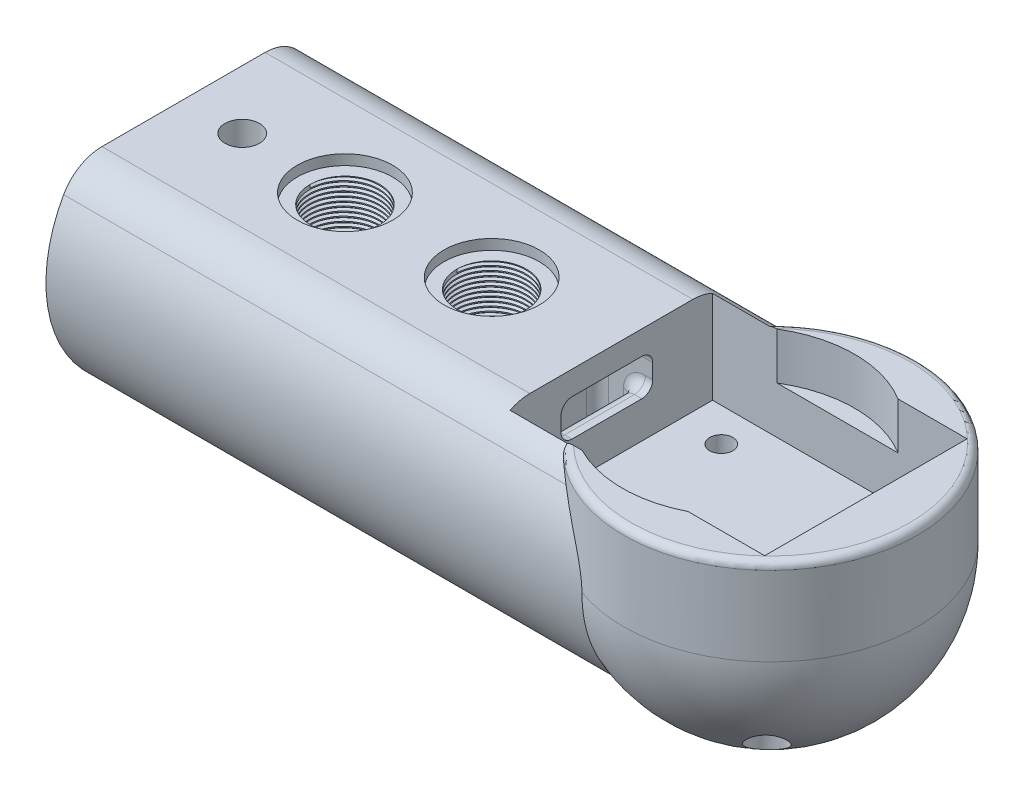
SolidWorks part; units mm, degrees
ref_plane "Front Plane" through (0, 0, 0) normal (0, 0, 1) x (1, 0, 0)
ref_plane "Top Plane" through (0, 0, 0) normal (0, 1, 0) x (1, 0, 0)
ref_plane "Right Plane" through (0, 0, 0) normal (1, 0, 0) x (0, 0, -1)
sketch "Sketch1" plane through (0, 0, 0) normal (1, 0, 0) x (0, 0, -1)
  circle A0 centre (0, 0) radius 18.75
  dimension "D1" = 37.5
extrude "Boss-Extrude1" add sketch "Sketch1" along normal blind 80
sketch "Sketch2" plane through (0, 0, 0) normal (1, 0, 0) x (0, 0, -1)
  circle A0 centre (0, 0) radius 3
  dimension "D1" = 6
extrude "Cut-Extrude1" cut sketch "Sketch2" along normal blind 12
sketch "Sketch3" plane through (0, 0, 0) normal (1, 0, 0) x (0, 0, -1)
  circle A0 centre (0, 0) radius 5.9
  dimension "D1" = 11.8
extrude "Cut-Extrude3" cut sketch "Sketch3" along normal blind 3
ref_plane "Plane1" through (0, 18.75, 0) normal (0, 1, 0) x (1, 0, 0)
sketch "Sketch5" plane through (0, 0, 0) normal (0, 1, 0) x (1, 0, 0)
  line L0 (0, 0) -> (65, 0) construction
  line L1 (80, -18.75) -> (80, 18.75) construction
  line L2 (80, 0) -> (100, 0) construction
  line L3 (100, 0) -> (109.7094, 0) construction
  line L4 (80, 0) -> (65, 0) construction
  line L5 (80, 0) -> (80, -42.3157) construction
  line L6 (80, 20) -> (80, -20)
  arc A0 (80, -20) -> (80, 20) centre (80, 0) ccw
  dimension "D1" = 40
revolve "Revolve95" add sketch "Sketch5" angle 180 about L5 reverse direction yes
sketch "Sketch23" plane through (0, 18.75, 0) normal (0, 1, 0) x (1, 0, 0)
  line L0 (80, -18.75) -> (73.0403, -18.75) construction
  line L1 (0, 18.75) -> (85, 18.75)
  line L2 (0, 18.75) -> (0, -18.75)
  line L3 (0, -18.75) -> (85, -18.75)
  line L4 (85, 18.75) -> (85, -18.75)
extrude "Cut-Extrude14" cut sketch "Sketch23" against normal blind 6.5
ref_plane "Plane7" through (0, 0, 0) normal (0, 1, 0) x (1, 0, 0)
sketch "Sketch26" plane through (0, 0, 0) normal (0, 1, 0) x (1, 0, 0)
  line L0 (0, 0) -> (118.1144, 0) construction
  line L1 (80, -18.75) -> (80, 18.75) construction
  circle A0 centre (80, 0) radius 20
  dimension "D1" = 40
extrude "Boss-Extrude8" add sketch "Sketch26" along normal blind 12.5
ref_plane "Plane9" through (0, 12.5, 0) normal (0, 1, 0) x (1, 0, 0)
fillet "Fillet9" radius 6 2 edges at (32.9555, 12.25, -14.1951) (32.9555, 12.25, 14.1951)
sketch "Sketch28" plane through (0, 12.5, 0) normal (0, 1, 0) x (1, 0, 0)
  line L0 (0, 0) -> (117.3111, 0) construction
  line L2 (58.3, 13.8) -> (93, 13.8)
  line L3 (58.3, 13.8) -> (58.3, -13.8)
  line L4 (58.3, -13.8) -> (93, -13.8)
  line L5 (93, 13.8) -> (93, -13.8)
  circle A0 centre (80, 0) radius 20 construction
  point P13 (100, 0)
  dimension "D1" = 34.7
  dimension "D2" = 27.6
  dimension "D3" = 13.8
  dimension "D4" = 7
extrude "Cut-Extrude16" cut sketch "Sketch28" against normal blind 13.5
ref_plane "Plane10" through (0, -1, 0) normal (0, 1, 0) x (1, 0, 0)
sketch "Sketch29" plane through (0, -1, 0) normal (0, 1, 0) x (1, 0, 0)
  line L0 (0, 0) -> (112.771, 0) construction
  line L1 (93, -13.8) -> (93, 13.8) construction
  line L2 (75.5, 24.0476) -> (75.5, -24.0476) construction
  line L3 (93, 13.8) -> (65.5238, 13.8) construction
  line L5 (93, -13.8) -> (93, 13.8) construction
  line L6 (89.92, -10.43) -> (64.07, -10.43) construction
  line L7 (64.07, 18.499) -> (64.07, -18.499) construction
  line L8 (89.92, 9.22) -> (64.07, 9.22) construction
  circle A0 centre (89.92, 9.22) radius 1.575
  circle A5 centre (89.92, -10.43) radius 1.575
  circle A7 centre (64.07, -10.43) radius 1.575
  circle A8 centre (64.07, 9.22) radius 1.575
  point P3 (75.5, 0)
  point P9 (75.5, 0)
  point P32 (64.07, 0)
  dimension "D2" = 3.15
  dimension "D5" = 19.65
  dimension "D1" = 17.5
  dimension "D3" = 4.58
  dimension "D4" = 3.08
  dimension "D6" = 25.85
extrude "Cut-Extrude17" cut sketch "Sketch29" against normal blind 13.5
ref_plane "Plane11" through (0, 12.5, 0) normal (0, 1, 0) x (1, 0, 0)
ref_plane "Plane13" through (58.3, 0, 0) normal (1, 0, 0) x (0, 0, -1)
sketch "Sketch31" plane through (58.3, 0, 0) normal (1, 0, 0) x (0, 0, -1)
  line L0 (15.18, -1) -> (-15.18, -1) construction
  line L1 (-6.85, 9) -> (5.65, 9)
  line L2 (-6.85, 9) -> (-6.85, 4)
  line L3 (-6.85, 4) -> (5.65, 4)
  line L4 (5.65, 9) -> (5.65, 4)
  line L5 (-13.8, -1) -> (-13.8, 12.5) construction
  point P8 (-13.8, 5.75)
  point P9 (-6.85, 6.5)
  dimension "D1" = 5
  dimension "D2" = 12.5
  dimension "D3" = 5
  dimension "D4" = 6.95
ref_plane "Plane17" through (0, 12.25, 0) normal (0, 1, 0) x (1, 0, 0)
sketch "Sketch35" plane through (0, 12.25, 0) normal (0, 1, 0) x (1, 0, 0)
  line L0 (0, 0) -> (45.8276, 0) construction
  line L1 (0, 0) -> (0, 21.2118) construction
  line L2 (12, 10) -> (52, 10) construction
  line L3 (12, 10) -> (12, -10) construction
  line L4 (12, -10) -> (52, -10) construction
  line L5 (52, 10) -> (52, -10) construction
  line L6 (32, 10) -> (32, -13.8872) construction
  circle A0 centre (22, 0) radius 6.5
  circle A1 centre (42, 0) radius 6.5
  dimension "D4" = 13
  dimension "D1" = 40
  dimension "D2" = 20
  dimension "D3" = 10
  dimension "D5" = 10
  dimension "D6" = 12
extrude "Cut-Extrude19" cut sketch "Sketch35" against normal blind 1.4
sketch "Sketch36" plane through (0, 12.25, 0) normal (0, 1, 0) x (1, 0, 0)
  line L0 (0, 0) -> (111.355, 0) construction
  circle A0 centre (22, 0) radius 4.75
  circle A1 centre (42, 0) radius 4.75
  dimension "D1" = 9.5
extrude "Cut-Extrude20" cut sketch "Sketch36" against normal blind 9.6
sketch "Sketch37" plane through (0, 12.25, 0) normal (0, 1, 0) x (1, 0, 0)
  line L0 (0, 0) -> (93.5041, 0) construction
  circle A0 centre (22, 0) radius 4
  circle A1 centre (42, 0) radius 4
  dimension "D1" = 8
extrude "Cut-Extrude21" cut sketch "Sketch37" against normal blind 22.6
extrude "Cut-Extrude22" cut sketch "Sketch31" against normal blind 7.5
ref_plane "Plane20" through (0, 4, 0) normal (0, 1, 0) x (1, 0, 0)
sketch "Sketch43" plane through (0, 4, 0) normal (0, 1, 0) x (1, 0, 0)
  line L0 (50.8, 5.65) -> (58.3, 5.65) construction
  line L1 (50.8, -6.85) -> (55.8, -6.85)
  line L2 (50.8, -6.85) -> (50.8, 5.65)
  line L3 (50.8, 5.65) -> (55.8, 5.65)
  line L4 (55.8, -6.85) -> (55.8, 5.65)
  dimension "D1" = 5
extrude "Cut-Extrude23" cut sketch "Sketch43" against normal blind 16
ref_plane "Plane21" through (50.8, 0, 0) normal (1, 0, 0) x (0, 0, -1)
sketch "Sketch44" plane through (50.8, 0, 0) normal (1, 0, 0) x (0, 0, -1)
  line L0 (5.65, -12) -> (5.65, 4) construction
  line L1 (-6.85, -12) -> (5.65, -12)
  line L2 (-6.85, -12) -> (-6.85, -7)
  line L3 (-6.85, -7) -> (5.65, -7)
  line L4 (5.65, -12) -> (5.65, -7)
  dimension "D1" = 5
extrude "Cut-Extrude24" cut sketch "Sketch44" against normal blind 45
ref_plane "Plane22" through (0, -12, 0) normal (0, 1, 0) x (1, 0, 0)
sketch "Sketch45" plane through (0, -12, 0) normal (0, 1, 0) x (1, 0, 0)
  line L0 (55.8, 5.65) -> (5.8, 5.65) construction
  line L1 (5.8, -6.85) -> (10.8, -6.85)
  line L2 (5.8, -6.85) -> (5.8, 5.65)
  line L3 (5.8, 5.65) -> (10.8, 5.65)
  line L4 (10.8, -6.85) -> (10.8, 5.65)
  dimension "D1" = 5
extrude "Cut-Extrude26" cut sketch "Sketch45" against normal blind 30.44
fillet "Fillet10" radius 1.5 22 edges at (10.8, -12, 0.6) (5.8, -7, 0.6) (55.8, -12, 0.6) (55.8, 4, 0.6) (50.8, -7, 0.6) (50.8, 9, 0.6) (57.05, 4, -5.65) (57.05, 4, 6.85) (28.3, -7, 6.85) (50.8, 1, -5.65) (33.3, -12, 6.85) (33.3, -12, -5.65) (54.55, 9, -5.65) (54.55, 9, 6.85) (55.8, -4, -5.65) (55.8, -4, 6.85) (50.8, 1, 6.85) (28.3, -7, -5.65) (10.8, -14.727, 6.85) (10.8, -14.9392, -5.65) (5.8, -12.4392, -5.65) (5.8, -12.227, 6.85)
thread "Thread1" pitch 0.6 method cut profile "Thread Profile1" start angle 0, offset 0, length 8, pitch 0.6, diameter 9.5
ref_plane "Plane23" through (17.25, 10.85, 0) normal (0, 0, 1) x (-1, 0, 0)
sketch "Thread Profile1" plane through (17.25, 10.85, 0) normal (0, 0, 1) x (-1, 0, 0)
  line L0 (0, 0) -> (0, 0.6) construction
  line L1 (0, 0) -> (0.3248, 0.1875)
  line L2 (0.3248, 0.1875) -> (0.3248, 0.2625)
  line L3 (0.3248, 0.2625) -> (0, 0.45)
  line L4 (0.3248, 0.225) -> (0, 0.225) construction
  line L11 (0, 0) -> (0, 0.45)
  point P2 (0, 0)
  dimension "Pitch" = 0.6
  dimension "Profile_Angle" = 60
  dimension "Profile_Land" = 0.075
  dimension "Profile_Height" = 0.3248
thread "Thread2" pitch 0.6 method cut profile "Thread Profile2" start angle 0, offset 0, length 8, pitch 0.6, diameter 9.5
ref_plane "Plane24" through (37.25, 10.85, 0) normal (0, 0, 1) x (-1, 0, 0)
sketch "Thread Profile2" plane through (37.25, 10.85, 0) normal (0, 0, 1) x (-1, 0, 0)
  line L0 (0, 0) -> (0, 0.6) construction
  line L1 (0, 0) -> (0.3248, 0.1875)
  line L2 (0.3248, 0.1875) -> (0.3248, 0.2625)
  line L3 (0.3248, 0.2625) -> (0, 0.45)
  line L4 (0.3248, 0.225) -> (0, 0.225) construction
  line L11 (0, 0) -> (0, 0.45)
  point P2 (0, 0)
  dimension "Pitch" = 0.6
  dimension "Profile_Angle" = 60
  dimension "Profile_Land" = 0.075
  dimension "Profile_Height" = 0.3248
ref_plane "Plane25" through (0, -20, 0) normal (0, -1, 0) x (-1, 0, 0)
sketch "Sketch60" plane through (0, -20, 0) normal (0, -1, 0) x (-1, 0, 0)
  line L0 (-89.92, 9.22) -> (-64.07, 9.22) construction
  line L1 (-89.92, -10.43) -> (-89.92, 9.22) construction
  line L2 (-89.92, -10.43) -> (-64.07, -10.43) construction
  line L3 (-64.07, -10.43) -> (-64.07, 9.22) construction
  line L4 (-76.995, 9.22) -> (-76.995, -10.43) construction
  line L5 (-64.07, -0.605) -> (-89.92, -0.605) construction
  circle A0 centre (-89.92, 9.22) radius 2.35
  circle A1 centre (-89.92, -10.43) radius 2.35
  circle A2 centre (-64.07, -10.43) radius 2.35
  circle A3 centre (-64.07, 9.22) radius 2.35
  dimension "D1" = 4.7
extrude "Cut-Extrude28" cut sketch "Sketch60" against normal blind 13
sketch "Sketch61" plane through (0, 12.25, 0) normal (0, 1, 0) x (1, 0, 0)
  line L0 (0, 0) -> (102.3285, 0) construction
  line L1 (0, 11.1131) -> (0, -11.1131) construction
  circle A0 centre (8, 0) radius 2.35
  dimension "D1" = 4.7
  dimension "D2" = 8
extrude "Cut-Extrude32" cut sketch "Sketch61" against normal blind 10
sketch "Sketch62" plane through (0, 12.5, 0) normal (0, 1, 0) x (1, 0, 0)
  circle A0 centre (80, 0) radius 20
  dimension "D1" = 40
extrude "Cut-Extrude34" cut sketch "Sketch62" against normal blind 0.7
sketch "Sketch63" plane through (0, 12.5, 0) normal (0, 1, 0) x (1, 0, 0)
  line L0 (93, 13.8) -> (93, -13.8) construction
  line L2 (65.5238, 13.8) -> (93, 13.8) construction
  circle A0 centre (75.34, 0.29) radius 15.83
  dimension "D1" = 31.66
  dimension "D2" = 17.66
  dimension "D3" = 13.51
extrude "Cut-Extrude35" cut sketch "Sketch63" against normal blind 7.07
fillet "Fillet11" radius 1 1 edges at (100, 11.8, 0)
